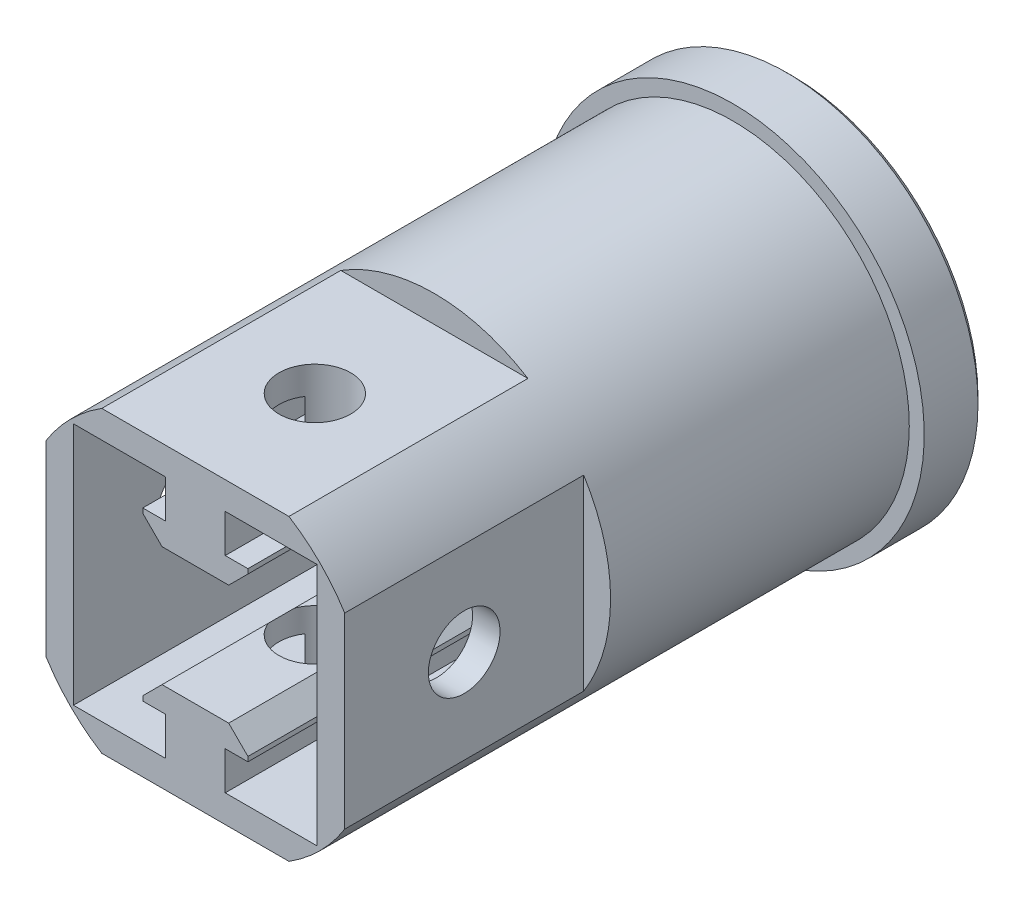
SolidWorks part; units mm, degrees
ref_plane "Front Plane" through (0, 0, 0) normal (0, 0, 1) x (1, 0, 0)
ref_plane "Top Plane" through (0, 0, 0) normal (0, 1, 0) x (1, 0, 0)
ref_plane "Right Plane" through (0, 0, 0) normal (1, 0, 0) x (0, 0, -1)
sketch "Sketch1" plane through (0, 0, 0) normal (0, 0, 1) x (1, 0, 0)
  line L0 (0, -15) -> (0, 15) construction
  line L6 (0, -10.2) -> (0, 10.2) construction
  line L7 (0, 10.2) -> (-10.2, 10.2) construction
  line L8 (-10.2, 10.2) -> (-2.5, 10.2)
  line L9 (-2.5, 10.2) -> (-2.5, 7)
  line L10 (-2.5, 7) -> (0, 7) construction
  line L11 (-2.5, 7) -> (-4.4, 7)
  line L12 (-4.4, 7) -> (-4.4, 6.61)
  line L13 (-4.4, 6.61) -> (-2.79, 5)
  line L14 (-2.79, 5) -> (0, 5) construction
  line L15 (-2.79, 5) -> (2.79, 5)
  line L16 (-10.2, 10.2) -> (0, 0) construction
  line L22 (-10.2, 10.2) -> (-10.2, 2.5)
  line L23 (0, 0) -> (-11.0308, 0) construction
  line L24 (4.4, 6.61) -> (2.79, 5)
  line L25 (4.4, 7) -> (4.4, 6.61)
  line L26 (2.5, 7) -> (4.4, 7)
  line L27 (2.5, 10.2) -> (2.5, 7)
  line L28 (10.2, 10.2) -> (2.5, 10.2)
  line L29 (10.2, 10.2) -> (10.2, 2.5)
  line L35 (-10.2, -10.2) -> (0, 0) construction
  line L36 (-2.79, -5) -> (0, -5) construction
  line L37 (-2.5, -7) -> (0, -7) construction
  line L38 (0, -10.2) -> (-10.2, -10.2) construction
  line L43 (10.2, -10.2) -> (10.2, -2.5)
  line L44 (10.2, -10.2) -> (2.5, -10.2)
  line L45 (2.5, -10.2) -> (2.5, -7)
  line L46 (2.5, -7) -> (4.4, -7)
  line L47 (4.4, -7) -> (4.4, -6.61)
  line L48 (4.4, -6.61) -> (2.79, -5)
  line L49 (-10.2, -10.2) -> (-10.2, -2.5)
  line L54 (-2.79, -5) -> (2.79, -5)
  line L55 (-4.4, -6.61) -> (-2.79, -5)
  line L56 (-4.4, -7) -> (-4.4, -6.61)
  line L57 (-2.5, -7) -> (-4.4, -7)
  line L58 (-2.5, -10.2) -> (-2.5, -7)
  line L59 (-10.2, -10.2) -> (-2.5, -10.2)
  line L60 (-10.2, -2.5) -> (-10.2, 2.5)
  line L61 (10.2, -2.5) -> (10.2, 2.5)
  circle A0 centre (0, 0) radius 14.75
  point P43 (5, 0)
  point P58 (-5, 0)
  dimension "D6" = 90
  dimension "D9" = 29.5
  dimension "D1" = 2.5
  dimension "D2" = 2.79
  dimension "D3" = 1.9
  dimension "D4" = 135
  dimension "D5" = 2
  dimension "D7" = 3.2
  dimension "D8" = 10.2
extrude "Boss-Extrude1" add sketch "Sketch1" along normal blind 50
sketch "Sketch6" plane through (0, 0, 0) normal (0, 0, -1) x (-1, 0, 0)
  circle A5 centre (0, 0) radius 16
  circle A8 centre (0, 0) radius 14.75
extrude "Boss-Extrude4" add sketch "Sketch6" against normal blind 5
sketch "Sketch7" plane through (0, 0, 50) normal (0, 0, 1) x (1, 0, 0)
  line L0 (0, 12.5) -> (0, -12.5) construction
  line L1 (0, -12.5) -> (11.0666, -12.5)
  line L2 (11.0666, -12.5) -> (11.0666, -16.553)
  line L3 (11.0666, -16.553) -> (-11.3408, -16.553)
  line L4 (-11.3408, -16.553) -> (-11.3408, -12.5)
  line L5 (-11.3408, -12.5) -> (0, -12.5)
  line L6 (0, 0) -> (-12.1635, 0) construction
  line L7 (-11.3408, 12.5) -> (0, 12.5)
  line L8 (-11.3408, 16.553) -> (-11.3408, 12.5)
  line L9 (11.0666, 16.553) -> (-11.3408, 16.553)
  line L10 (11.0666, 12.5) -> (11.0666, 16.553)
  line L11 (0, 12.5) -> (11.0666, 12.5)
  line L12 (0, 0) -> (-7.1098, -7.1098) construction
  line L13 (0, 0) -> (0, -12.1635) construction
  line L14 (12.5, 0) -> (-12.5, 0) construction
  line L15 (12.5, 0) -> (12.5, 11.0666)
  line L16 (12.5, 11.0666) -> (16.553, 11.0666)
  line L17 (16.553, 11.0666) -> (16.553, -11.3408)
  line L18 (16.553, -11.3408) -> (12.5, -11.3408)
  line L19 (12.5, -11.3408) -> (12.5, 0)
  line L20 (-12.5, -11.3408) -> (-12.5, 0)
  line L21 (-16.553, -11.3408) -> (-12.5, -11.3408)
  line L22 (-16.553, 11.0666) -> (-16.553, -11.3408)
  line L23 (-12.5, 11.0666) -> (-16.553, 11.0666)
  line L24 (-12.5, 0) -> (-12.5, 11.0666)
extrude "Cut-Extrude3" cut sketch "Sketch7" against normal blind 20
sketch "Sketch8" plane through (0, -12.5, 0) normal (0, -1, 0) x (1, 0, 0)
  line L0 (-7.8302, 40) -> (7.8302, 40) construction
  line L1 (-7.8302, 30) -> (-7.8302, 50) construction
  line L2 (7.8302, 50) -> (7.8302, 30) construction
  circle A0 centre (0, 40) radius 3
extrude "Cut-Extrude4" cut sketch "Sketch8" against normal through all
ref_axis "Axis1" through (0, 0, -2.5) along (0, 0, 1)
ref_plane "Plane2" through (0, 0, 0) normal (0.7071, -0.7071, 0) x (0, 0, -1)
mirror "Mirror1" about plane through (0, 0, 0) normal (0.7071, -0.7071, 0) of "Cut-Extrude4"
chamfer "Chamfer2" distance 0.5 angle 45 25 edges at (-4.4, 6.805, 0) (-3.595, 5.805, 0) (0, 5, 0) (3.595, 5.805, 0) (4.4, 6.805, 0) (3.45, 7, 0) (2.5, 8.6, 0) (6.35, 10.2, 0) (10.2, 0, 0) (6.35, -10.2, 0) (2.5, -8.6, 0) (3.45, -7, 0) (4.4, -6.805, 0) (3.595, -5.805, 0) (0, -5, 0) (-3.595, -5.805, 0) (-4.4, -6.805, 0) (-3.45, -7, 0) (-2.5, -8.6, 0) (-6.35, -10.2, 0) (-10.2, 0, 0) (-6.35, 10.2, 0) (-2.5, 8.6, 0) (-3.45, 7, 0) (-16, 0, 0)
